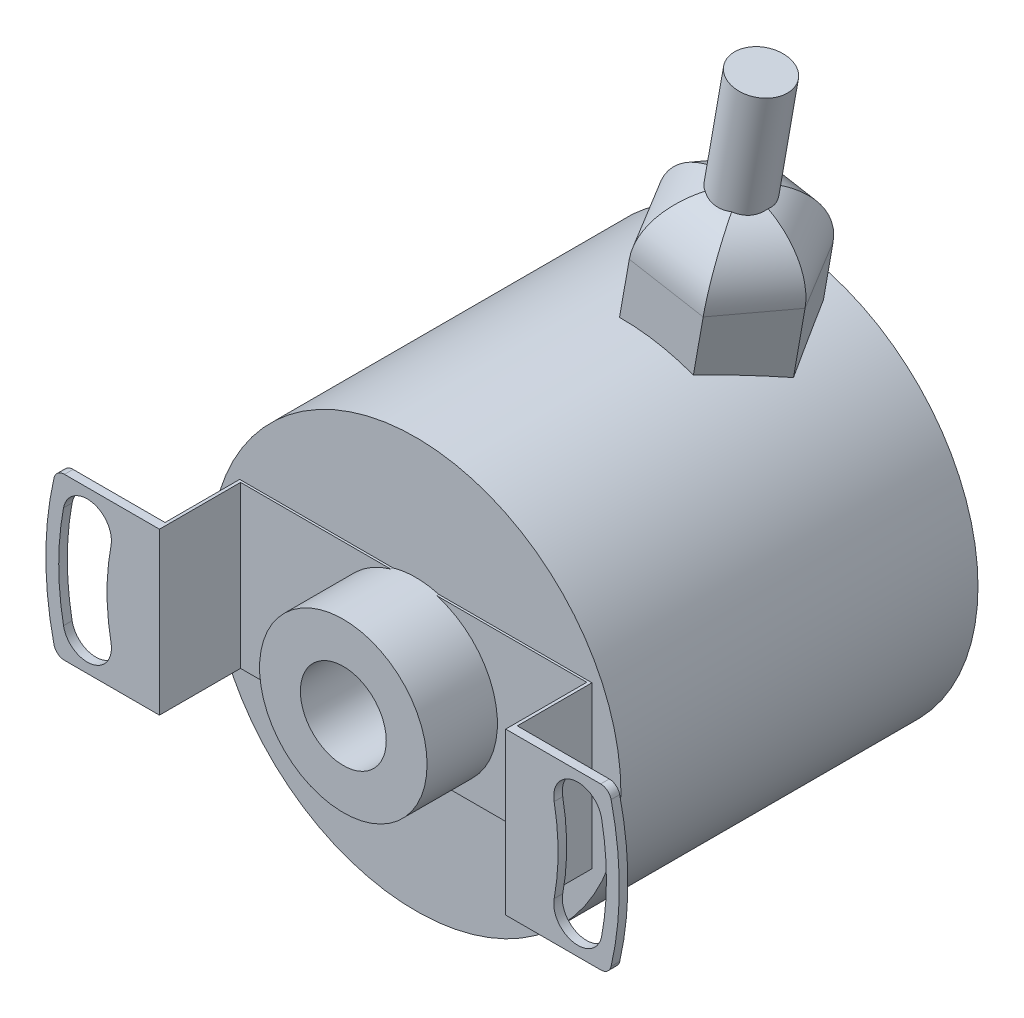
SolidWorks part; units mm, degrees
ref_plane "Front Plane" through (0, 0, 0) normal (0, 0, 1) x (1, 0, 0)
ref_plane "Top Plane" through (0, 0, 0) normal (0, 1, 0) x (1, 0, 0)
ref_plane "Right Plane" through (0, 0, 0) normal (1, 0, 0) x (0, 0, -1)
sketch "Sketch1" plane through (0, 0, 0) normal (0, 0, 1) x (1, 0, 0)
  circle A0 centre (0, 0) radius 19.1
  dimension "D1" = 38.2
extrude "Boss-Extrude1" add sketch "Sketch1" against normal blind 33.25
sketch "Sketch2" plane through (0, 0, 0) normal (0, 0, 1) x (1, 0, 0)
  circle A0 centre (0, 0) radius 7.8
  circle A1 centre (0, 0) radius 4
  dimension "D1" = 15.6
  dimension "D2" = 8
extrude "Boss-Extrude2" add sketch "Sketch2" along normal offset from surface (6.75 mm away) 40 contours A0 A1 region at (-7.5794, 0, 0) up to face at (19.1, 0, -33.25)
sketch "Sketch3" plane through (0, 0, 0) normal (0, 1, 0) x (1, 0, 0)
  line L0 (26.7, -6.95) -> (26.7, -7.75)
  line L1 (26.7, -7.75) -> (16.12, -7.75)
  line L2 (16.12, -7.75) -> (16.12, -0.2)
  line L3 (16.12, -0.2) -> (0, -0.2)
  line L4 (0, -0.2) -> (0, 0)
  line L5 (0, 0) -> (16.4, 0)
  line L6 (-19.1, 0) -> (19.1, 0) construction
  line L7 (16.4, 0) -> (16.4, -6.95)
  line L8 (16.4, -6.95) -> (26.7, -6.95)
  line L9 (19.1, 33.25) -> (-19.1, 33.25) construction
  line L12 (0, 0) -> (0, -8.7132) construction
  dimension "D1" = 41
  dimension "D2" = 0.8
  dimension "D3" = 0.28
  dimension "D4" = 0.2
  dimension "D5" = 32.8
  dimension "D6" = 53.4
extrude "Boss-Extrude4" add sketch "Sketch3" along normal mid plane 15
sketch "Sketch4" plane through (0, 0, 7.75) normal (0, 0, 1) x (1, 0, 0)
  line L0 (16.12, 7.5) -> (26.7, 7.5) construction
  line L1 (16.12, -7.5) -> (26.7, -7.5) construction
  line L2 (26.7, 7.5) -> (26.7, -7.5) construction
  line L3 (0, 0) -> (0, 17.1823) construction
  line L4 (16.12, -7.5) -> (26.7, -7.5)
  line L5 (16.12, 7.5) -> (26.7, 7.5)
  line L6 (26.7, 7.5) -> (26.7, -7.5)
  line L7 (0, 0) -> (23.25, 0) construction
  line L8 (19.9413, 6.58) -> (24.7904, 6.58) construction
  arc A0 (25.75, 7.5) -> (25.75, -7.5) centre (-3.3803, 0) cw
  arc A1 (22.8432, -4.33) -> (22.8432, 4.33) centre (0, 0) ccw construction
  arc A2 (25.0539, -4.749) -> (25.0539, 4.749) centre (0, 0) ccw
  arc A3 (20.6326, -3.911) -> (20.6326, 3.911) centre (0, 0) ccw
  arc A4 (20.6326, -3.911) -> (25.0539, -4.749) centre (22.8432, -4.33) ccw
  arc A5 (25.0539, 4.749) -> (20.6326, 3.911) centre (22.8432, 4.33) ccw
  point P12 (23.25, 0)
  point P17 (25.5, 0)
  point P18 (26.7, 0)
  line M9 (26.7, -7.5) -> (26.7, 7.5)
  line M10 (26.7, 7.5) -> (16.12, 7.5)
  dimension "D2" = 2.25
  dimension "D1" = 51.5
  dimension "D3" = 1.2
  dimension "D4" = 1.84
extrude "Cut-Extrude1" cut sketch "Sketch4" against normal up to next contours A2 A5 A3 A4 | A0 L4 M9 | A0 L6 M10 region at (26.4158, -5.631, 7.75) region at (26.4158, 5.631, 7.75) region at (23.036, 0, 7.75)
fillet "Fillet1" radius 1 2 edges at (25.75, -7.5, 7.35) (25.75, 7.5, 7.35)
mirror "Mirror2" about plane through (0, 0, 0) normal (1, 0, 0) of "Cut-Extrude1", "Boss-Extrude4", "Fillet1"
extrude "Cut-Extrude2" cut sketch "Sketch2<3>" against normal blind 13.6 from surface contours A1 region at (0, 0, 0) starting at face at (4, 0, 6.75)
sketch "Sketch2<3>" plane through (0, 0, 0) normal (0, 0, 1) x (1, 0, 0) same geometry as "Sketch2"
ref_axis "Axis1" through (0, 0, -33.25) along (0, 0, 1)
ref_plane "Plane1" through (0, 0, 0) normal (0.1736, 0.9848, 0) x (0, 0, 1)
sketch "Sketch5" plane through (0, 0, 0) normal (0.1736, 0.9848, 0) x (0, 0, 1)
  line L0 (-33.25, 0) -> (0, 0) construction
  line L1 (-31.25, -3.493) -> (-25.2, -6.9859)
  line L2 (-25.2, -6.9859) -> (-19.15, -3.493)
  line L3 (-19.15, -3.493) -> (-19.15, 3.493)
  line L4 (-19.15, 3.493) -> (-25.2, 6.9859)
  line L5 (-25.2, 6.9859) -> (-31.25, 3.493)
  line L6 (-31.25, 3.493) -> (-31.25, -3.493)
  line L7 (-33.25, 19.1) -> (-33.25, -19.1) construction
  circle A0 centre (-25.2, 0) radius 6.05 construction
  dimension "D1" = 12.1
  dimension "D2" = 2
extrude "Boss-Extrude5" add sketch "Sketch5" along normal blind 30
fillet "Fillet2" radius 6 6 edges at (10.3693, 28.6344, -28.225) (10.3693, 28.6344, -22.175) (5.2094, 29.5442, -19.15) (0.0496, 30.4541, -22.175) (0.0496, 30.4541, -28.225) (5.2094, 29.5442, -31.25)
sketch "Sketch6" plane through (0, 0, 0) normal (0.1736, 0.9848, 0) x (0, 0, 1)
  line L0 (-25.15, 0.0289) -> (-25.2, 0.0577) construction
  line L1 (-25.2, -0.0577) -> (-25.15, -0.0289) construction
  line L2 (-25.25, 0.0289) -> (-25.25, -0.0289) construction
  circle A0 centre (-25.2, 0) radius 0.05 construction
  circle A1 centre (-25.2, 0) radius 2.5
  dimension "D1" = 5
extrude "Boss-Extrude6" add sketch "Sketch6" along normal blind 40
